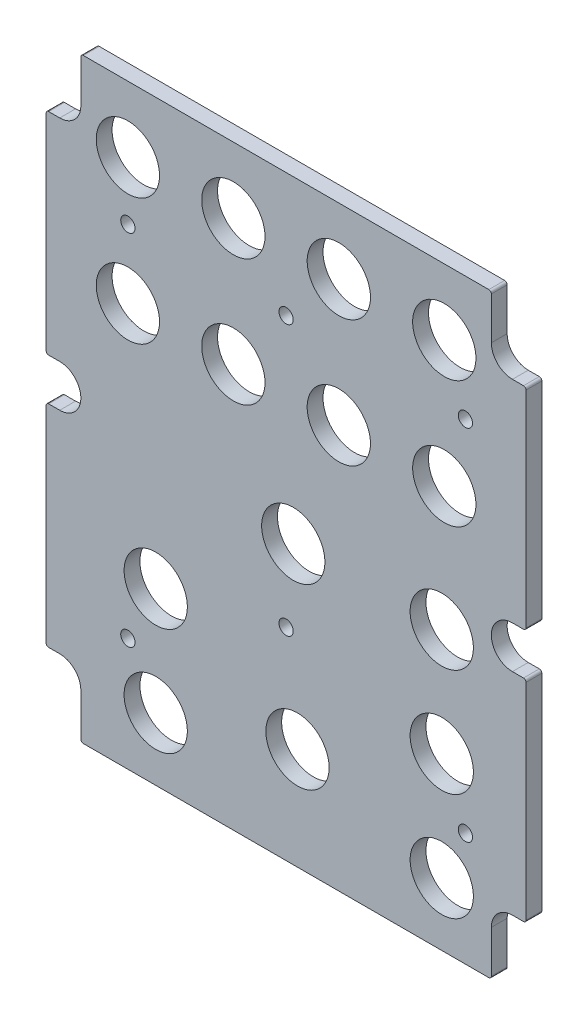
SolidWorks part; units mm, degrees
ref_plane "Front Plane" through (0, 0, 0) normal (0, 0, 1) x (1, 0, 0)
ref_plane "Top Plane" through (0, 0, 0) normal (0, 1, 0) x (1, 0, 0)
ref_plane "Right Plane" through (0, 0, 0) normal (1, 0, 0) x (0, 0, -1)
sketch "Sketch1" plane through (0, 0, -4.2926) normal (0, 0, 1) x (1, 0, 0)
  line L18 (11.2395, 14.2875) -> (11.2395, 1.5558)
  line L19 (12.0015, 0.7938) -> (134.0485, 0.7938)
  line L20 (134.8105, 1.5558) -> (134.8105, 14.2875)
  line L21 (141.1605, 20.6375) -> (144.4943, 20.6375)
  line L22 (145.2563, 21.3995) -> (145.2563, 83.3755)
  line L23 (144.4943, 84.1375) -> (141.1605, 84.1375)
  line L24 (141.1605, 96.8375) -> (144.4942, 96.8375)
  line L25 (145.2562, 97.5995) -> (145.2562, 159.5755)
  line L26 (144.4942, 160.3375) -> (141.1605, 160.3375)
  line L27 (134.8105, 166.6875) -> (134.8105, 179.4192)
  line L28 (134.0485, 180.1812) -> (12.0015, 180.1812)
  line L29 (11.2395, 179.4192) -> (11.2395, 166.6875)
  line L30 (4.8895, 160.3375) -> (1.5558, 160.3375)
  line L31 (0.7938, 159.5755) -> (0.7938, 97.5995)
  line L32 (1.5557, 96.8375) -> (4.8895, 96.8375)
  line L33 (4.8895, 84.1375) -> (1.5557, 84.1375)
  line L34 (0.7937, 83.3755) -> (0.7938, 21.3995)
  line L35 (1.5558, 20.6375) -> (4.8895, 20.6375)
  line L36 (11.2395, 14.2875) -> (11.2395, 1.5558)
  line L37 (12.0015, 0.7938) -> (134.0485, 0.7938)
  line L38 (134.8105, 1.5558) -> (134.8105, 14.2875)
  line L39 (141.1605, 20.6375) -> (144.4943, 20.6375)
  line L40 (145.2563, 21.3995) -> (145.2563, 83.3755)
  line L41 (144.4943, 84.1375) -> (141.1605, 84.1375)
  line L42 (141.1605, 96.8375) -> (144.4942, 96.8375)
  line L43 (145.2562, 97.5995) -> (145.2562, 159.5755)
  line L44 (144.4942, 160.3375) -> (141.1605, 160.3375)
  line L45 (134.8105, 166.6875) -> (134.8105, 179.4192)
  line L46 (134.0485, 180.1812) -> (12.0015, 180.1812)
  line L47 (11.2395, 179.4192) -> (11.2395, 166.6875)
  line L48 (4.8895, 160.3375) -> (1.5558, 160.3375)
  line L49 (0.7938, 159.5755) -> (0.7938, 97.5995)
  line L50 (1.5557, 96.8375) -> (4.8895, 96.8375)
  line L51 (4.8895, 84.1375) -> (1.5557, 84.1375)
  line L52 (0.7937, 83.3755) -> (0.7938, 21.3995)
  line L53 (1.5558, 20.6375) -> (4.8895, 20.6375)
  arc A18 (11.2395, 14.2875) -> (4.8895, 20.6375) centre (4.8895, 14.2875) ccw
  arc A19 (11.2395, 1.5558) -> (12.0015, 0.7938) centre (12.0015, 1.5558) ccw
  arc A20 (134.0485, 0.7938) -> (134.8105, 1.5558) centre (134.0485, 1.5558) ccw
  arc A21 (141.1605, 20.6375) -> (134.8105, 14.2875) centre (141.1605, 14.2875) ccw
  arc A22 (144.4943, 20.6375) -> (145.2563, 21.3995) centre (144.4943, 21.3995) ccw
  arc A23 (145.2563, 83.3755) -> (144.4943, 84.1375) centre (144.4943, 83.3755) ccw
  arc A24 (141.1605, 96.8375) -> (141.1605, 84.1375) centre (141.1605, 90.4875) ccw
  arc A25 (144.4942, 96.8375) -> (145.2562, 97.5995) centre (144.4942, 97.5995) ccw
  arc A26 (145.2562, 159.5755) -> (144.4942, 160.3375) centre (144.4942, 159.5755) ccw
  arc A27 (134.8105, 166.6875) -> (141.1605, 160.3375) centre (141.1605, 166.6875) ccw
  arc A28 (134.8105, 179.4192) -> (134.0485, 180.1812) centre (134.0485, 179.4192) ccw
  arc A29 (12.0015, 180.1812) -> (11.2395, 179.4192) centre (12.0015, 179.4192) ccw
  arc A30 (4.8895, 160.3375) -> (11.2395, 166.6875) centre (4.8895, 166.6875) ccw
  arc A31 (1.5558, 160.3375) -> (0.7938, 159.5755) centre (1.5558, 159.5755) ccw
  arc A32 (0.7938, 97.5995) -> (1.5557, 96.8375) centre (1.5557, 97.5995) ccw
  arc A33 (4.8895, 84.1375) -> (4.8895, 96.8375) centre (4.8895, 90.4875) ccw
  arc A34 (1.5557, 84.1375) -> (0.7937, 83.3755) centre (1.5557, 83.3755) ccw
  arc A35 (0.7938, 21.3995) -> (1.5558, 20.6375) centre (1.5557, 21.3995) ccw
  arc A36 (11.2395, 14.2875) -> (4.8895, 20.6375) centre (4.8895, 14.2875) ccw
  arc A37 (11.2395, 1.5558) -> (12.0015, 0.7938) centre (12.0015, 1.5558) ccw
  arc A38 (134.0485, 0.7938) -> (134.8105, 1.5558) centre (134.0485, 1.5558) ccw
  arc A39 (141.1605, 20.6375) -> (134.8105, 14.2875) centre (141.1605, 14.2875) ccw
  arc A40 (144.4943, 20.6375) -> (145.2563, 21.3995) centre (144.4943, 21.3995) ccw
  arc A41 (145.2563, 83.3755) -> (144.4943, 84.1375) centre (144.4943, 83.3755) ccw
  arc A42 (141.1605, 96.8375) -> (141.1605, 84.1375) centre (141.1605, 90.4875) ccw
  arc A43 (144.4942, 96.8375) -> (145.2562, 97.5995) centre (144.4942, 97.5995) ccw
  arc A44 (145.2562, 159.5755) -> (144.4942, 160.3375) centre (144.4942, 159.5755) ccw
  arc A45 (134.8105, 166.6875) -> (141.1605, 160.3375) centre (141.1605, 166.6875) ccw
  arc A46 (134.8105, 179.4192) -> (134.0485, 180.1812) centre (134.0485, 179.4192) ccw
  arc A47 (12.0015, 180.1812) -> (11.2395, 179.4192) centre (12.0015, 179.4192) ccw
  arc A48 (4.8895, 160.3375) -> (11.2395, 166.6875) centre (4.8895, 166.6875) ccw
  arc A49 (1.5558, 160.3375) -> (0.7938, 159.5755) centre (1.5558, 159.5755) ccw
  arc A50 (0.7938, 97.5995) -> (1.5557, 96.8375) centre (1.5557, 97.5995) ccw
  arc A51 (4.8895, 84.1375) -> (4.8895, 96.8375) centre (4.8895, 90.4875) ccw
  arc A52 (1.5557, 84.1375) -> (0.7937, 83.3755) centre (1.5557, 83.3755) ccw
  arc A53 (0.7938, 21.3995) -> (1.5558, 20.6375) centre (1.5557, 21.3995) ccw
  dimension "D1" = 0
extrude "Boss-Extrude1" add sketch "Sketch1" along normal blind 4.7625
hole_wizard "3/4 (0.75) Diameter Hole1" positions "Sketch3" profile "Sketch2" hole size "3/4" standard "ANSI Inch" end condition through all
sketch "Sketch3" plane through (0, 0, 0.4699) normal (0, 0, 1) x (1, 0, 0)
  point P0 (33.782, 19.685)
  point P3 (76.454, 31.496)
  point P6 (119.888, 19.685)
  point P9 (119.888, 52.07)
  point P12 (33.782, 52.07)
  point P15 (75.184, 84.455)
  point P18 (119.888, 84.455)
  point P21 (25.4, 122.2248)
  point P24 (57.15, 122.2248)
  point P27 (88.9, 122.2248)
  point P30 (120.65, 122.2248)
  point P33 (25.4, 160.3248)
  point P36 (57.15, 160.3248)
  point P39 (88.9, 160.3248)
  point P42 (120.65, 160.3248)
sketch "Sketch2" plane through (33.782, 19.685, 0.4699) normal (1, 0, 0) x (0, -1, 0)
  line L0 (0, 0) -> (0, 4.7625)
  line L1 (0, 4.7625) -> (9.525, 4.7625)
  line L2 (9.525, 4.7625) -> (9.525, 0)
  line L5 (9.525, 0) -> (0, 0)
  line L11 (0, -6.35) -> (0, 107.95) construction
  dimension "Thru Hole Dia." = 19.05
  dimension "Thru Hole Depth" = 4.7625
hole_wizard "#6 Clearance Hole1" positions "Sketch5" profile "Sketch4" hole size "#6" standard "ANSI Inch" end condition through all
sketch "Sketch5" plane through (0, 0, 0.4699) normal (0, 0, 1) x (1, 0, 0)
  point P0 (25.4, 142.875)
  point P3 (73.025, 142.875)
  point P6 (127, 142.875)
  point P9 (73.025, 61.647)
  point P12 (25.4, 34.925)
  point P15 (127, 34.925)
sketch "Sketch4" plane through (25.4, 142.875, 0.4699) normal (1, 0, 0) x (0, -1, 0)
  line L0 (0, 0) -> (0, 4.7625)
  line L1 (0, 4.7625) -> (2.1526, 4.7625)
  line L2 (2.1526, 4.7625) -> (2.1526, 0)
  line L5 (2.1526, 0) -> (0, 0)
  line L11 (0, -6.35) -> (0, 107.95) construction
  dimension "Thru Hole Dia." = 4.3053
  dimension "Thru Hole Depth" = 4.7625
